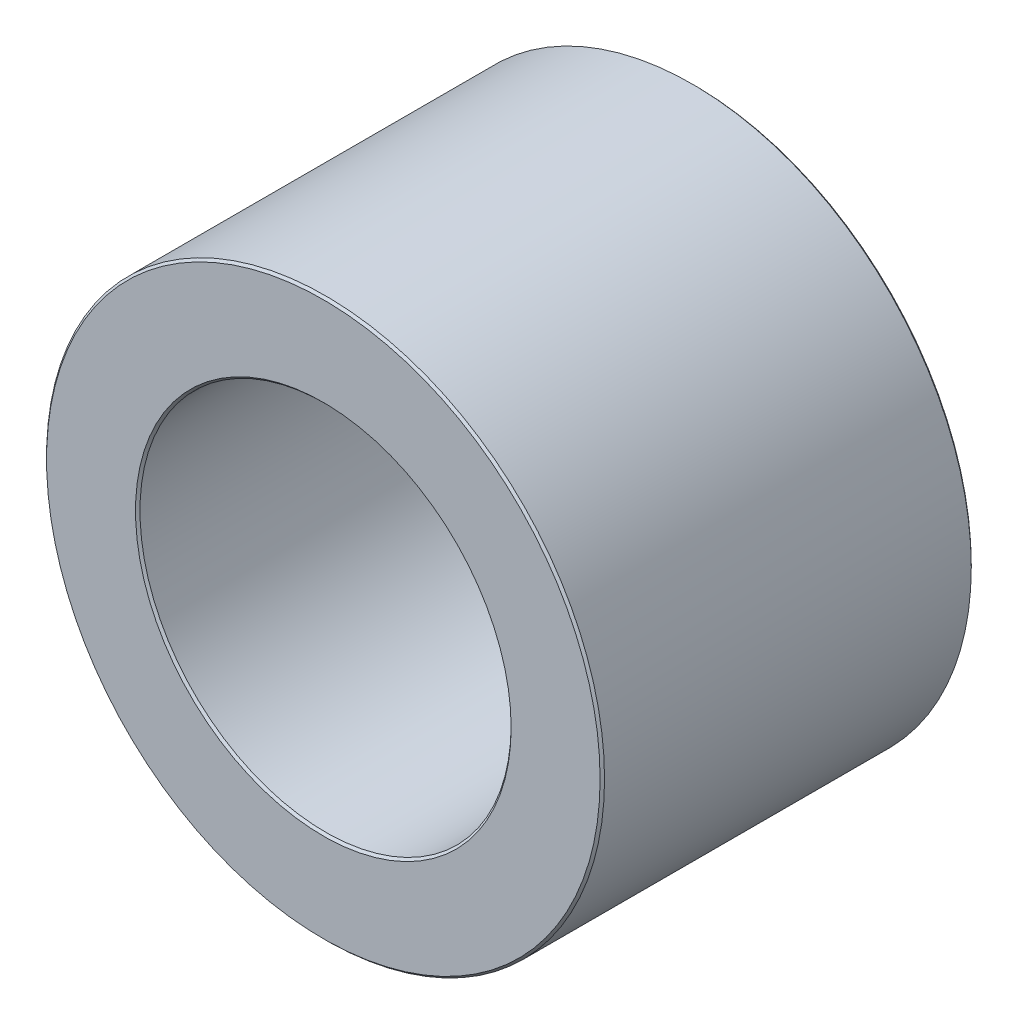
SolidWorks part; units mm, degrees
ref_plane "Front Plane" through (0, 0, 0) normal (0, 0, 1) x (1, 0, 0)
ref_plane "Top Plane" through (0, 0, 0) normal (0, 1, 0) x (1, 0, 0)
ref_plane "Right Plane" through (0, 0, 0) normal (1, 0, 0) x (0, 0, -1)
sketch "Sketch1" plane through (0, 0, 0) normal (0, 0, 1) x (1, 0, 0)
  circle A0 centre (0, 0) radius 4.51
  circle A1 centre (0, 0) radius 3
  point P8 (0, -4.51)
  point P9 (0, 4.51)
  dimension "ID" = 6
  dimension "OD" = 9.02
sketch "Sketch2" plane through (0, 0, 0) normal (1, 0, 0) x (0, 0, -1)
  line L0 (3, 0) -> (-3, 0) construction
  line L1 (3, 4.51) -> (-3, 4.51) construction
  point P4 (0, 0)
  point P8 (0, 4.51)
  point P9 (0, 4.51)
  dimension "Length" = 6
sketch "Sketch5" plane through (0, 0, 0) normal (0, 0, 1) x (1, 0, 0)
  circle A0 centre (0, 0) radius 3 construction
  circle A1 centre (0, 0) radius 4.51 construction
  circle A2 centre (0, 0) radius 3
  circle A3 centre (0, 0) radius 4.51
extrude "Boss-Extrude1" add sketch "Sketch5" along normal up to vertex and the other way up to vertex up to point (0, 0, 3) other way up to point (0, 0, -3)
chamfer "Chamfer1" distance 0.036 angle 45 4 edges at (4.51, 0, -3) (3, 0, -3) (3, 0, 3) (4.51, 0, 3)
equation "\"D1@Chamfer1\"=\"ID@Sketch1\"*.006"
